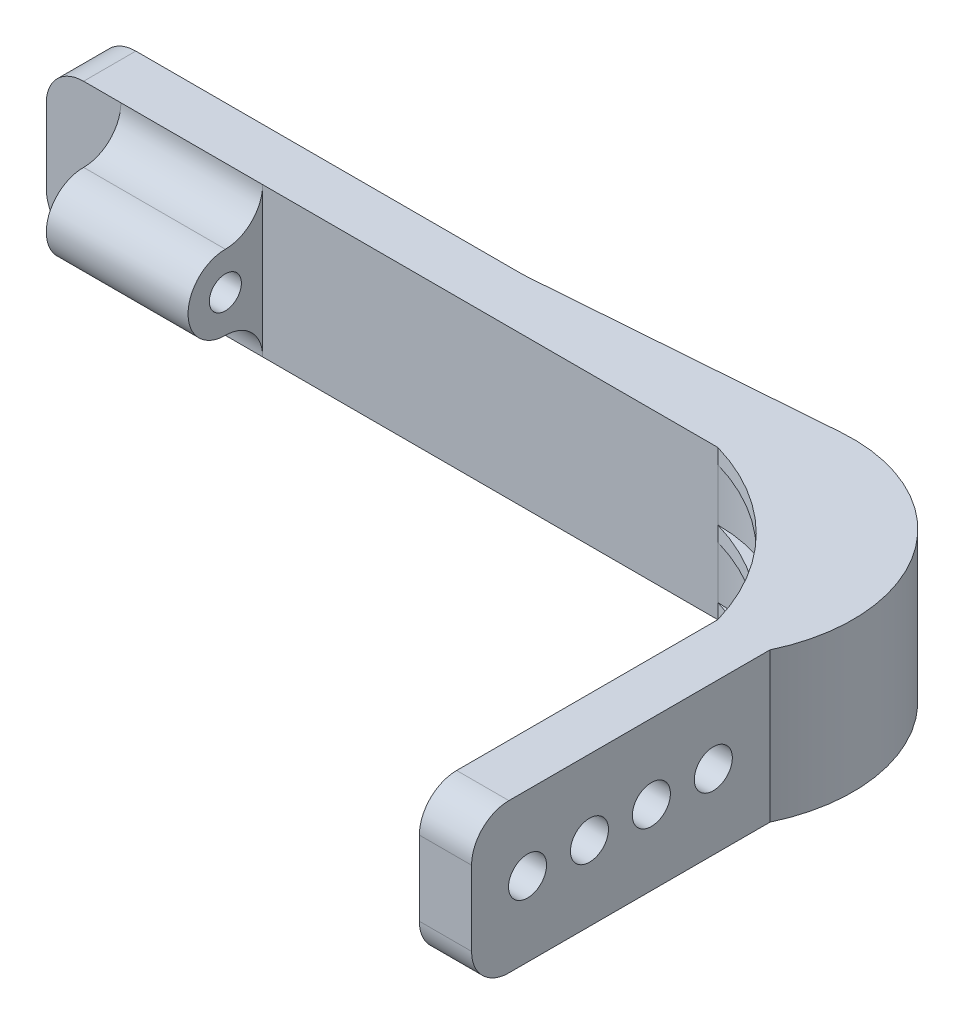
SolidWorks part; units mm, degrees
ref_plane "Front Plane" through (0, 0, 0) normal (0, 0, 1) x (1, 0, 0)
ref_plane "Top Plane" through (0, 0, 0) normal (0, 1, 0) x (1, 0, 0)
ref_plane "Right Plane" through (0, 0, 0) normal (1, 0, 0) x (0, 0, -1)
sketch "Sketch1" plane through (0, 0, 0) normal (0, 1, 0) x (1, 0, 0)
  line L0 (0, 0) -> (90, 0)
  line L1 (117, -27) -> (117, -67)
  line L2 (0, -7) -> (90, -7)
  line L3 (110, -27) -> (110, -67)
  line L4 (110, -67) -> (117, -67)
  line L5 (0, -7) -> (0, 0)
  arc A0 (90, 0) -> (117, -27) centre (90, -27) cw
  arc A1 (90, -7) -> (110, -27) centre (90, -27) cw
  dimension "D4" = 20
  dimension "D2" = 90
  dimension "D3" = 40
  dimension "D1" = 7
extrude "Boss-Extrude1" add sketch "Sketch1" along normal blind 20
ref_plane "Plane1" through (0, 0, 65) normal (0, 0, 1) x (1, 0, 0)
sketch "Sketch3" plane through (0, 0, 65) normal (0, 0, 1) x (1, 0, 0)
  line L6 (117, 12) -> (117, 8)
  line L8 (117, 20) -> (117, 0) construction
  line L9 (117, 8) -> (120, 5)
  line L10 (120, 5) -> (120, 15)
  line L11 (120, 15) -> (117, 12)
  line L12 (117, 10) -> (120, 10) construction
  line L13 (110, 20) -> (117, 20) construction
  dimension "D1" = 10
  dimension "D2" = 4
  dimension "D3" = 3
  dimension "D4" = 10
extrude "Boss-Extrude3" [suppressed] add sketch "Sketch3" against normal blind 40
sketch "Sketch4" plane through (0, 0, 0) normal (1, 0, 0) x (0, 0, -1)
  line L0 (-27, 20) -> (-67, 20) construction
  line L1 (-67, 20) -> (-67, 0) construction
  circle A0 centre (-59.5, 10) radius 2.55
  dimension "D1" = 5.1
  dimension "D2" = 10
  dimension "D3" = 7.5
extrude "Cut-Extrude1" cut sketch "Sketch4" along normal through all
pattern_linear "LPattern1" count 4 spacing 8.3 along (0, 0, -1) of "Cut-Extrude1"
sketch "Sketch5" plane through (0, 0, 0) normal (0, 0, 1) x (1, 0, 0)
  line L0 (90, 20) -> (0, 20) construction
  line L1 (0, 20) -> (0, 0) construction
  circle A0 centre (15, 10) radius 2.55
  dimension "D1" = 5.1
  dimension "D2" = 10
  dimension "D3" = 15
fillet "Fillet2" radius 5 4 edges at (113.5, 0, 67) (113.5, 20, 67) (0, 0, 3.5) (0, 20, 3.5)
sketch "Sketch6" plane through (0, 0, 0) normal (0, 1, 0) x (1, 0, 0)
  line L0 (90, 0) -> (5, 0) construction
  line L1 (57.068, 0) -> (96.4605, 3)
  line L2 (90, 0) -> (57.068, 0)
  line L6 (110, -27) -> (110, -62)
  line L7 (110, -62) -> (117, -62)
  line L8 (117, -62) -> (117, -27)
  line L9 (90, 0) -> (5, 0)
  line L10 (5, 0) -> (5, -7)
  line L11 (5, -7) -> (90, -7)
  arc A0 (117, -27) -> (96.4605, 3) centre (98.0552, -17.9394) ccw
  arc A3 (117, -27) -> (90, 0) centre (90, -27) ccw
  arc A8 (117, -27) -> (90, 0) centre (90, -27) ccw
  arc A9 (110, -27) -> (90, -7) centre (90, -27) ccw
  dimension "D2" = 21
  dimension "D3" = 3
  dimension "D1" = 0
extrude "Boss-Extrude4" add sketch "Sketch6" along normal up to surface (20 mm away) up to face at (81.7168, 20, 22.7832)
sketch "Sketch8" plane through (0, 0, 0) normal (0, 1, 0) x (1, 0, 0)
  arc A0 (90, -7) -> (110, -27) centre (81.8988, -35.1012) cw
  arc A1 (90, -7) -> (110, -27) centre (90, -27) cw
extrude "Boss-Extrude5" add sketch "Sketch8" along normal blind 2
pattern_linear "LPattern3" count 3 spacing 9 along (0, 1, 0) of "Boss-Extrude5"
fillet "Fillet4" radius 20 1 edges at (57.068, 10, 0)
ref_plane "Plane2" through (10, 0, 0) normal (-1, 0, 0) x (0, 0, 1)
sketch "Sketch9" plane through (10, 0, 0) normal (-1, 0, 0) x (0, 0, 1)
  line L0 (2.3062, 10) -> (15.0365, 10) construction
  line L1 (0, 20) -> (7, 20) construction
  line L2 (7, 15) -> (12, 15)
  line L3 (7, 18) -> (7, 11) construction
  line L4 (7, 5) -> (12, 5)
  line L5 (7, 9) -> (7, 2) construction
  line L6 (7, 15) -> (7, 5)
  arc A0 (12, 15) -> (12, 5) centre (12, 10) cw
  circle A1 centre (12, 10) radius 2.15
  point P16 (17, 10)
  dimension "D6" = 5
  dimension "D7" = 4.3
  dimension "D1" = 10
  dimension "D2" = 5
  dimension "D3" = 5
  dimension "D4" = 5
  dimension "D5" = 5
  dimension "D8" = 5
extrude "Boss-Extrude6" add sketch "Sketch9" against normal blind 19
fillet "Fillet5" radius 5 2 edges at (19.5, 5, 7) (19.5, 15, 7)
